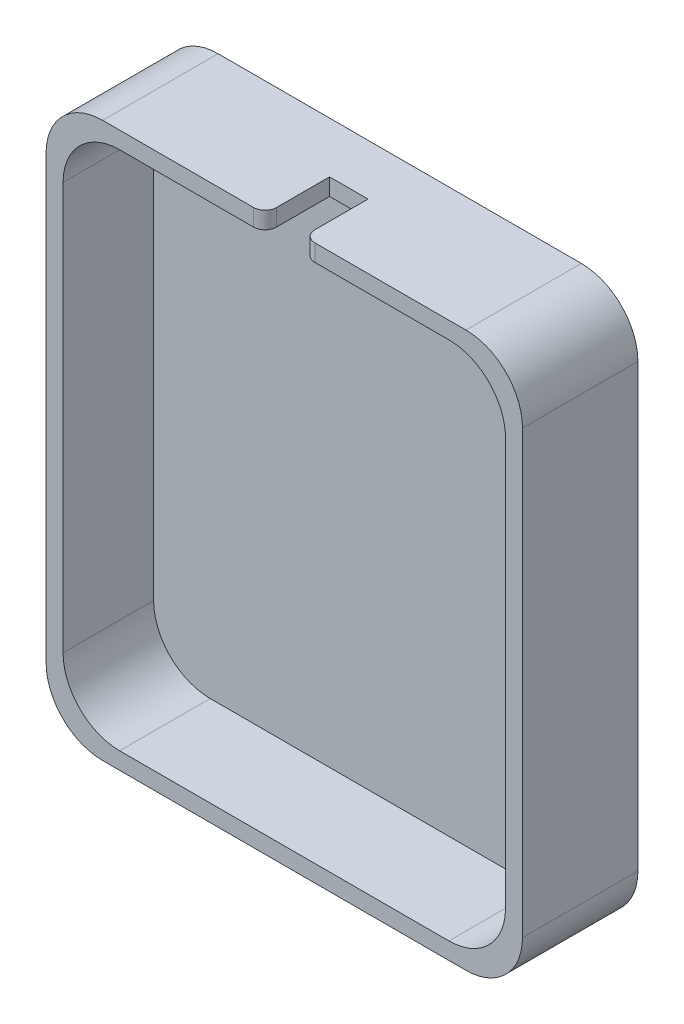
SolidWorks part; units mm, degrees
ref_plane "Front Plane" through (0, 0, 0) normal (0, 0, 1) x (1, 0, 0)
ref_plane "Top Plane" through (0, 0, 0) normal (0, 1, 0) x (1, 0, 0)
ref_plane "Right Plane" through (0, 0, 0) normal (1, 0, 0) x (0, 0, -1)
sketch "Sketch1" plane through (0, 0, 0) normal (0, 0, 1) x (1, 0, 0)
  line L1 (19.55, 23) -> (-19.55, 23)
  line L2 (19.55, 23) -> (19.55, -23)
  line L3 (19.55, -23) -> (-19.55, -23)
  line L4 (-19.55, 23) -> (-19.55, -23)
  line L5 (19.55, 23) -> (-19.55, -23) construction
  line L6 (19.55, -23) -> (-19.55, 23) construction
  line L7 (21.05, 24.5) -> (-21.05, 24.5)
  line L8 (21.05, 24.5) -> (21.05, -24.5)
  line L9 (21.05, -24.5) -> (-21.05, -24.5)
  line L10 (-21.05, 24.5) -> (-21.05, -24.5)
  line L11 (21.05, 24.5) -> (-21.05, -24.5) construction
  line L12 (21.05, -24.5) -> (-21.05, 24.5) construction
  point P0 (0, 0)
  point P6 (0, 0)
  dimension "D1" = 46
  dimension "D2" = 39.1
  dimension "D3" = 1.5
  dimension "D4" = 1.5
extrude "Boss-Extrude1" add sketch "Sketch1" along normal blind 8
extrude "Boss-Extrude2" add sketch "Sketch1<2>" against normal blind 2.2 contours L10 L9 L8 L7
sketch "Sketch1<2>" plane through (0, 0, 0) normal (0, 0, 1) x (1, 0, 0) same geometry as "Sketch1"
fillet "Fillet1" radius 5 8 edges at (21.05, -24.5, 2.9) (21.05, 24.5, 2.9) (-21.05, 24.5, 2.9) (-21.05, -24.5, 2.9) (19.55, -23, 4) (-19.55, -23, 4) (19.55, 23, 4) (-19.55, 23, 4)
sketch "Sketch2" plane through (0, 24.5, 0) normal (0, 1, 0) x (1, 0, 0)
  line L0 (-21.05, 0.7) -> (21.05, 0.7)
  line L1 (-21.05, -8) -> (-21.05, 2.2) construction
  line L2 (21.05, 2.2) -> (21.05, -8) construction
  line L3 (16.05, 2.2) -> (-16.05, 2.2) construction
  line L4 (16.05, -8) -> (-16.05, -8) construction
  line L6 (1.7, -2.3) -> (1.7, -8)
  line L7 (1.7, -8) -> (-1.7, -8)
  line L8 (-1.7, -2.3) -> (-1.7, -8)
  line L9 (0, 0.7) -> (0, -8) construction
  line L10 (-1.7, -2.3) -> (1.7, -2.3)
  point P8 (0, 0)
  line M6 (-16.05, -8) -> (16.05, -8)
  dimension "D1" = 1.5
  dimension "D2" = 3.4
  dimension "D3" = 3
extrude "Cut-Extrude1" cut sketch "Sketch2" against normal blind 1.5 contours L9 L0 L8 M6 | L0 L9 L7 L6 region at (0, 24.5, 5.15)
fillet "Fillet2" radius 1 2 edges at (-1.7, 23.75, 8) (1.7, 23.75, 8)
sketch "Sketch3" plane through (0, 0, 0) normal (0, 0, 1) x (1, 0, 0)
  line L0 (-19.55, 0) -> (19.55, 0) construction
  line L1 (-19.55, 18) -> (-19.55, -18) construction
  line L2 (19.55, -18) -> (19.55, 18) construction
  line L4 (-14.55, -23) -> (14.55, -23) construction
  line L5 (0, -23) -> (0, 24.5) construction
  line L6 (-1.7, 24.5) -> (1.7, 24.5) construction
  circle A0 centre (0, 9.8) radius 1.375
  circle A1 centre (-9.75, 0) radius 1.375
  circle A2 centre (0, -9.8) radius 1.375
  circle A3 centre (9.75, 0) radius 1.375
  dimension "D1" = 2.75
  dimension "D2" = 9.8
  dimension "D3" = 9.8
extrude "Cut-Extrude2" cut sketch "Sketch3" against normal up to surface (2.2 mm away) up to face at (0, 0, -2.2)
sketch "Sketch4" plane through (0, 0, 0) normal (0, 0, 1) x (1, 0, 0)
  circle A0 centre (-9.75, 0) radius 1.5
  circle A1 centre (0, 9.8) radius 1.5
  circle A2 centre (9.75, 0) radius 1.5
  circle A3 centre (0, -9.8) radius 1.5
  dimension "D1" = 3
extrude "Boss-Extrude3" add sketch "Sketch4" against normal blind 0.2
